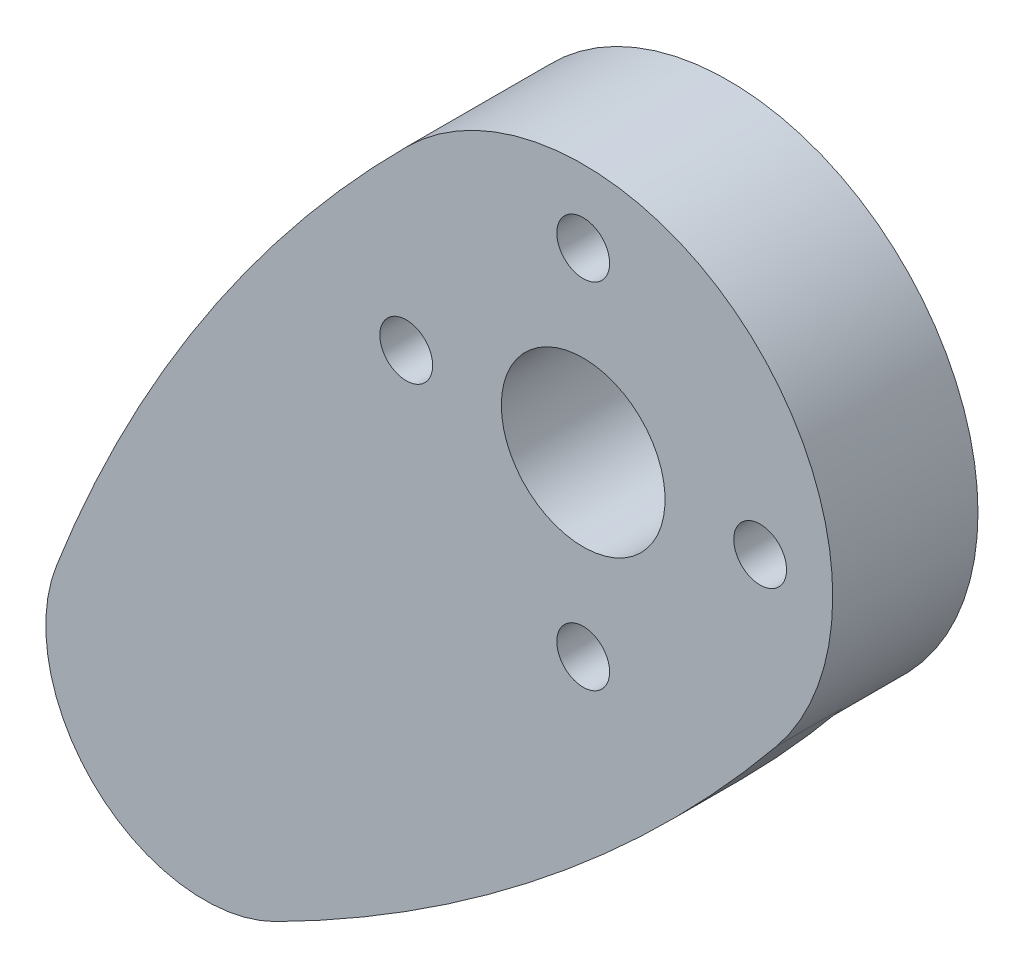
SolidWorks part; units mm, degrees
ref_plane "Front Plane" through (0, 0, 0) normal (0, 0, 1) x (1, 0, 0)
ref_plane "Top Plane" through (0, 0, 0) normal (0, 1, 0) x (1, 0, 0)
ref_plane "Right Plane" through (0, 0, 0) normal (1, 0, 0) x (0, 0, -1)
sketch "Sketch1" plane through (0, 0, 0) normal (0, 0, 1) x (1, 0, 0)
  line L0 (70.1254, 27.305) -> (58.42, 27.305) construction
  line L1 (58.42, 27.305) -> (58.42, 0) construction
  line L2 (58.42, 0) -> (99.06, 0) construction
  line L3 (99.06, 0) -> (99.06, 31.75) construction
  line L4 (99.06, 31.75) -> (73.66, 31.75) construction
  line L5 (73.66, 31.75) -> (73.66, 28.6195) construction
  line L6 (78.6801, 26.924) -> (87.4395, 26.924) construction
  line L7 (87.4395, 26.924) -> (87.4395, 24.13) construction
  line L8 (87.4395, 24.13) -> (80.9328, 22.479) construction
  line L9 (70.1254, 27.305) -> (58.42, 27.305)
  line L10 (58.42, 27.305) -> (58.42, 0)
  line L11 (58.42, 0) -> (99.06, 0)
  line L12 (99.06, 0) -> (99.06, 31.75)
  line L13 (99.06, 31.75) -> (73.66, 31.75)
  line L14 (73.66, 31.75) -> (73.66, 28.6195)
  line L15 (78.6801, 26.924) -> (87.4395, 26.924)
  line L16 (87.4395, 26.924) -> (87.4395, 24.13)
  line L17 (87.4395, 24.13) -> (80.9328, 22.479)
  line L18 (80.8812, 20.7957) -> (87.5941, 20.7957)
  line L19 (87.5941, 20.7957) -> (88.2812, 23.5039)
  line L20 (88.2812, 23.5039) -> (79.7909, 25.6582)
  line L21 (80.9328, 22.479) -> (87.4395, 26.924) construction
  line L22 (88.2812, 23.5039) -> (80.8812, 20.7957) construction
  line L23 (87.5941, 20.7957) -> (79.7909, 25.6582) construction
  line L24 (78.6801, 26.924) -> (87.4395, 24.13) construction
  line L25 (81.3178, 26.0826) -> (111.6739, 61.618) construction
  arc A0 (78.6801, 26.924) -> (73.66, 28.6195) centre (74.168, 21.844) ccw construction
  arc A1 (70.1254, 27.305) -> (80.9328, 22.479) centre (74.168, 21.844) ccw construction
  circle A2 centre (104.4893, 52.0065) radius 12 construction
  arc A3 (78.6801, 26.924) -> (73.66, 28.6195) centre (74.168, 21.844) ccw
  arc A4 (70.1254, 27.305) -> (80.9328, 22.479) centre (74.168, 21.844) ccw
  circle A5 centre (104.4893, 52.0065) radius 12
  circle A6 centre (56.226, 91.417) radius 74.31
  circle A7 centre (86.2672, 31.8764) radius 7.62
  circle A8 centre (148.4954, 7.8931) radius 74.31
  dimension "D2" = 15.24
  dimension "D1" = 46.736
extrude "Boss-Extrude1" add sketch "Sketch1" along normal blind 3.175 contours L13 A7 | L13 A7 L15 L16 | L15 A7 L16 | A7 A6 L12 L13 | A5 A8 A7 L13 L12 A6 | A5 region at (94.0508, 41.3164, 0) region at (104.4893, 52.0065, 0) region at (95.3834, 29.7296, 0) region at (86.5606, 29.0842, 0) region at (84.6642, 25.7868, 0) region at (86.2672, 35.0423, 0)
sketch "Sketch2" plane through (0, 0, 0) normal (0, 0, -1) x (-1, 0, 0)
  circle A0 centre (-104.4893, 52.0065) radius 12
extrude "Boss-Extrude2" add sketch "Sketch2" along normal blind 3.81
sketch "Sketch3" plane through (0, 0, -3.81) normal (0, 0, -1) x (-1, 0, 0)
  circle A1 centre (-104.4893, 52.0065) radius 12
  circle A2 centre (-104.4893, 52.0065) radius 12
  circle A4 centre (-104.4893, 52.0065) radius 3.937
  dimension "D2" = 7.874
  dimension "D1" = 0
extrude "Cut-Extrude1" cut sketch "Sketch3" against normal through all contours A4
sketch "Sketch4" plane through (0, 0, -3.81) normal (0, 0, -1) x (-1, 0, 0)
  line L0 (-104.4893, 60.5155) -> (-104.4893, 52.0065) construction
  line L1 (-104.4893, 52.0065) -> (-104.4893, 43.4975) construction
  line L2 (-104.4893, 52.0065) -> (-95.9803, 52.0065) construction
  line L3 (-104.4893, 52.0065) -> (-112.9983, 52.0065) construction
  circle A1 centre (-104.4893, 52.0065) radius 12
  circle A2 centre (-104.4893, 52.0065) radius 12
  circle A5 centre (-104.4893, 52.0065) radius 8.509 construction
  circle A6 centre (-95.9803, 52.0065) radius 1.27
  circle A7 centre (-112.9983, 52.0065) radius 1.27
  circle A8 centre (-104.4893, 43.4975) radius 1.27
  circle A9 centre (-104.4893, 60.5155) radius 1.27
  dimension "D2" = 17.018
  dimension "D3" = 2.54
  dimension "D1" = 0
extrude "Cut-Extrude2" cut sketch "Sketch4" against normal through all contours A7 | A6 | A9 | A8 region at (95.9803, 52.0065, -3.81) region at (112.9983, 52.0065, -3.81)
